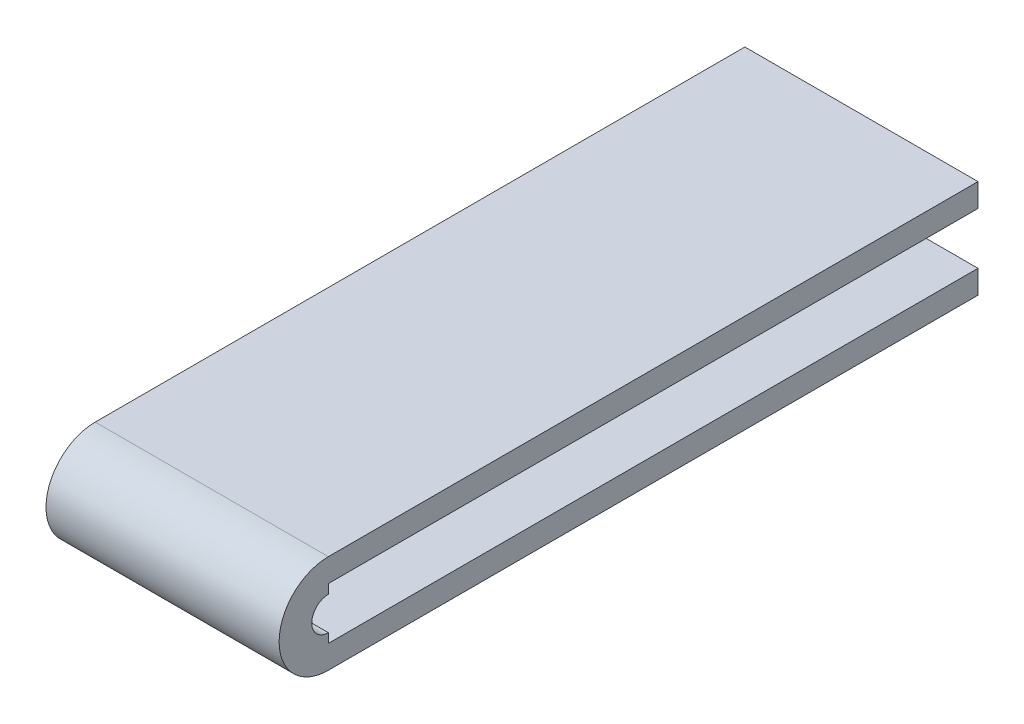
SolidWorks part; units mm, degrees
ref_plane "Front Plane" through (0, 0, 0) normal (0, 0, 1) x (1, 0, 0)
ref_plane "Top Plane" through (0, 0, 0) normal (0, 1, 0) x (1, 0, 0)
ref_plane "Right Plane" through (0, 0, 0) normal (1, 0, 0) x (0, 0, -1)
sketch "Sketch1" plane through (0, 0, 0) normal (1, 0, 0) x (0, 0, -1)
  line L0 (0, 2.032) -> (0, -2.032) construction
  line L1 (0, 6.0325) -> (79.6417, 6.0325)
  line L2 (0, 6.0325) -> (0, 2.032)
  line L3 (0, -6.0325) -> (79.6417, -6.0325)
  line L4 (79.6417, 6.0325) -> (79.6417, 3.175)
  line L5 (0, -2.032) -> (0, -6.0325)
  line L6 (79.6417, 3.175) -> (79.6417, -3.175) construction
  line L7 (0, 3.175) -> (79.6417, 3.175)
  line L8 (0, 3.175) -> (0, -3.175)
  line L9 (0, -3.175) -> (79.6417, -3.175)
  line L10 (79.6417, 3.175) -> (79.6417, -3.175) construction
  line L11 (79.6417, -3.175) -> (79.6417, -6.0325)
  arc A0 (0, 6.0325) -> (0, -6.0325) centre (0, 0) ccw
  arc A1 (0, 2.032) -> (0, -2.032) centre (0, 0) ccw
  arc A2 (0, -2.032) -> (0, 2.032) centre (0, 0) ccw construction
  arc A3 (0, -6.0325) -> (0, 6.0325) centre (0, 0) ccw construction
  point P12 (0, 0)
  dimension "D1" = 12.065
  dimension "D2" = 4.064
  dimension "D3" = 6.35
  dimension "D4" = 79.6417
extrude "Boss-Extrude1" add sketch "Sketch1" along normal blind 28.575 contours L2 L7 L4 L1 | A1 L2 A0 L5 | L11 L9 L5 L3 region at (0, 4.6037, -39.8208) region at (0, 0, 2.7776) region at (0, -4.6037, -39.8209)
